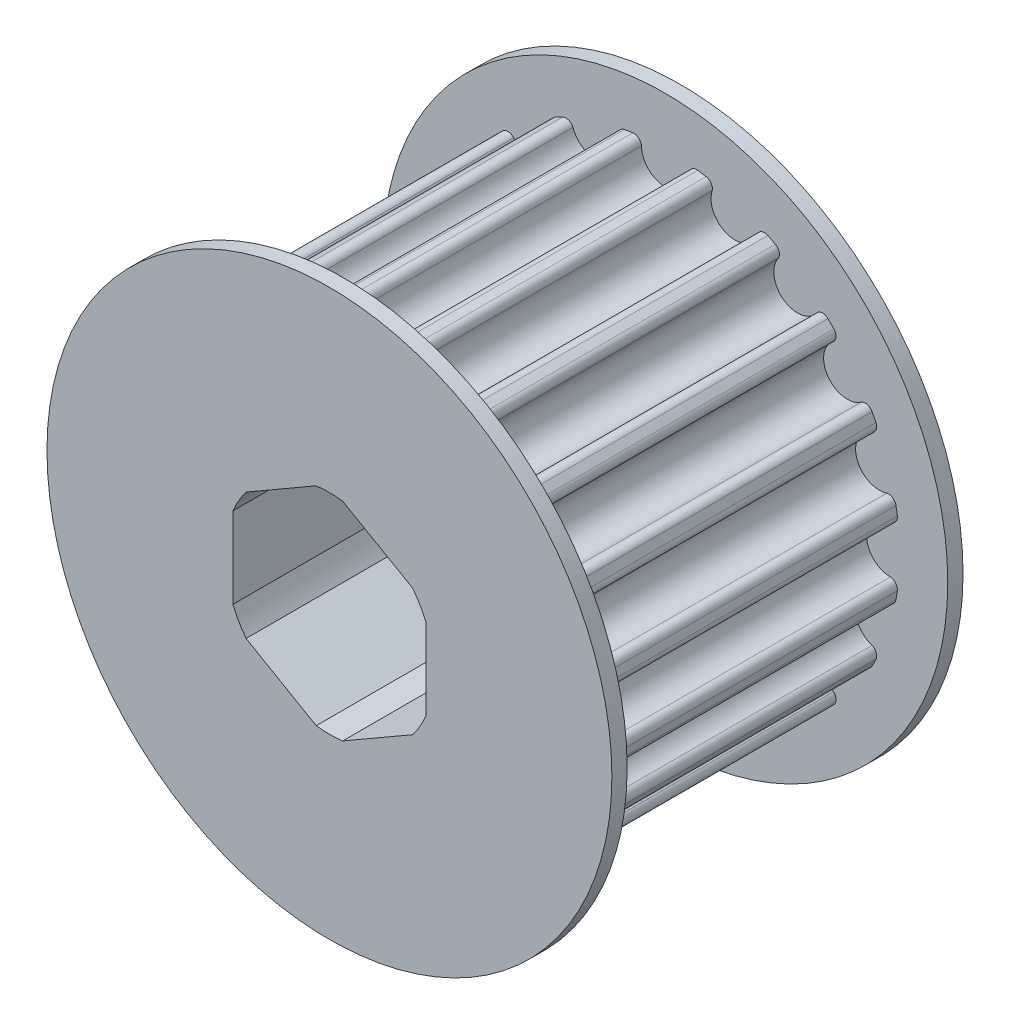
SolidWorks part; units mm, degrees
material "6061-T6 (SS)"
ref_plane "Front Plane" through (0, 0, 0) normal (0, 0, 1) x (1, 0, 0)
ref_plane "Top Plane" through (0, 0, 0) normal (0, 1, 0) x (1, 0, 0)
ref_plane "Right Plane" through (0, 0, 0) normal (1, 0, 0) x (0, 0, -1)
sketch "Pitch diameter" plane through (0, 0, 0) normal (0, 0, 1) x (1, 0, 0)
  circle A0 centre (0, 0) radius 15.9155 construction
  dimension "D1" = 31.831
sketch "Sketch2" plane through (0, 0, 0) normal (0, 0, 1) x (1, 0, 0)
  circle A0 centre (0, 0) radius 15.344
  dimension "D1" = 30.688
extrude "Boss-Extrude1" add sketch "Sketch2" along normal blind 21
sketch "Sketch3" plane through (0, 0, 0) normal (0, 0, -1) x (-1, 0, 0)
  line L0 (-1.6145, 15.2588) -> (-1.56, 14.744)
  line L1 (1.6145, 15.2588) -> (1.56, 14.744)
  line L2 (-1.56, 14.744) -> (1.56, 14.744) construction
  circle A0 centre (0, 0) radius 15.344 construction
  arc A1 (-1.56, 14.744) -> (1.56, 14.744) centre (0, 14.744) ccw
  circle A2 centre (0, 0) radius 15.344 construction
  arc A3 (1.6145, 15.2588) -> (-1.6145, 15.2588) centre (0, 0) ccw
  point P10 (0, 14.744)
  point P15 (0, 13.184)
  point P16 (0, 15.344)
  dimension "D1" = 1.56
  dimension "D2" = 2.16
extrude "Cut-Extrude1" cut sketch "Sketch3" against normal through all
fillet "Fillet1" radius 0.5 2 edges at (-1.6145, 15.2588, 10.5) (1.6145, 15.2588, 10.5)
pattern_circular "CirPattern1" count 20 over 360 about axis through (0, 0, 0) along (0, 0, 1) of "Cut-Extrude1", "Fillet1"
sketch "Sketch5" plane through (0, 0, 0) normal (0, 0, -1) x (-1, 0, 0)
  line L0 (0, 7.303) -> (-0.8658, 6.8031) construction
  line L1 (0.8658, -6.8031) -> (5.4588, -4.1514)
  line L2 (6.3246, -2.6517) -> (6.3246, 2.6517)
  line L3 (5.4588, 4.1514) -> (0.8658, 6.8031)
  line L4 (-0.8658, 6.8031) -> (-5.4588, 4.1514)
  line L5 (-6.3246, 2.6517) -> (-6.3246, -2.6517)
  line L6 (-5.4588, -4.1514) -> (-0.8658, -6.8031)
  line L7 (0.8658, 6.8031) -> (0, 7.303) construction
  line L8 (6.3246, 3.6515) -> (5.4588, 4.1514) construction
  line L9 (6.3246, 2.6517) -> (6.3246, 3.6515) construction
  line L10 (6.3246, -3.6515) -> (6.3246, -2.6517) construction
  line L11 (5.4588, -4.1514) -> (6.3246, -3.6515) construction
  line L12 (-0.8658, -6.8031) -> (0, -7.303) construction
  line L13 (0, -7.303) -> (0.8658, -6.8031) construction
  line L14 (-6.3246, -3.6515) -> (-5.4588, -4.1514) construction
  line L15 (-6.3246, -2.6517) -> (-6.3246, -3.6515) construction
  line L16 (-5.4588, 4.1514) -> (-6.3246, 3.6515) construction
  line L17 (-6.3246, 3.6515) -> (-6.3246, 2.6517) construction
  circle A1 centre (0, 0) radius 6.3246 construction
  arc A2 (-5.4588, 4.1514) -> (-6.3246, 2.6517) centre (0, 0) ccw
  arc A3 (-0.8658, 6.8031) -> (-5.4588, 4.1514) centre (0, 0) ccw construction
  arc A4 (5.4588, 4.1514) -> (0.8658, 6.8031) centre (0, 0) ccw construction
  arc A5 (0.8658, 6.8031) -> (-0.8658, 6.8031) centre (0, 0) ccw
  arc A6 (6.3246, -2.6517) -> (6.3246, 2.6517) centre (0, 0) ccw construction
  arc A7 (6.3246, 2.6517) -> (5.4588, 4.1514) centre (0, 0) ccw
  arc A8 (0.8658, -6.8031) -> (5.4588, -4.1514) centre (0, 0) ccw construction
  arc A9 (5.4588, -4.1514) -> (6.3246, -2.6517) centre (0, 0) ccw
  arc A10 (-5.4588, -4.1514) -> (-0.8658, -6.8031) centre (0, 0) ccw construction
  arc A11 (-0.8658, -6.8031) -> (0.8658, -6.8031) centre (0, 0) ccw
  arc A12 (-6.3246, 2.6517) -> (-6.3246, -2.6517) centre (0, 0) ccw construction
  arc A13 (-6.3246, -2.6517) -> (-5.4588, -4.1514) centre (0, 0) ccw
  dimension "D1" = 12.6492
  dimension "D2" = 12.6492
  dimension "D3" = 13.716
extrude "Cut-Extrude2" cut sketch "Sketch5" against normal through all contours L5 A13 L6 A11 L1 A9 L2 A7 L3 A5 L4 A2 region at (0, 0, 0)
ref_plane "Plane1" through (0, 0, 10.5) normal (0, 0, 1) x (1, 0, 0)
sketch "Sketch7" plane through (0, 0, 21) normal (0, 0, 1) x (1, 0, 0)
  line L18 (6.3246, -2.6517) -> (6.3246, 2.6517)
  line L19 (0.8658, -6.8031) -> (5.4588, -4.1514)
  line L20 (-5.4588, -4.1514) -> (-0.8658, -6.8031)
  line L21 (-6.3246, 2.6517) -> (-6.3246, -2.6517)
  line L22 (-0.8658, 6.8031) -> (-5.4588, 4.1514)
  line L23 (5.4588, 4.1514) -> (0.8658, 6.8031)
  line L24 (6.3246, -2.6517) -> (6.3246, 2.6517)
  line L25 (0.8658, -6.8031) -> (5.4588, -4.1514)
  line L26 (-5.4588, -4.1514) -> (-0.8658, -6.8031)
  line L27 (-6.3246, 2.6517) -> (-6.3246, -2.6517)
  line L28 (-0.8658, 6.8031) -> (-5.4588, 4.1514)
  line L29 (5.4588, 4.1514) -> (0.8658, 6.8031)
  circle A0 centre (0, 0) radius 18.5
  arc A7 (5.4588, -4.1514) -> (6.3246, -2.6517) centre (0, 0) ccw
  arc A8 (-0.8658, -6.8031) -> (0.8658, -6.8031) centre (0, 0) ccw
  arc A9 (-6.3246, -2.6517) -> (-5.4588, -4.1514) centre (0, 0) ccw
  arc A10 (-5.4588, 4.1514) -> (-6.3246, 2.6517) centre (0, 0) ccw
  arc A11 (0.8658, 6.8031) -> (-0.8658, 6.8031) centre (0, 0) ccw
  arc A12 (6.3246, 2.6517) -> (5.4588, 4.1514) centre (0, 0) ccw
  arc A13 (5.4588, -4.1514) -> (6.3246, -2.6517) centre (0, 0) ccw
  arc A14 (-0.8658, -6.8031) -> (0.8658, -6.8031) centre (0, 0) ccw
  arc A15 (-6.3246, -2.6517) -> (-5.4588, -4.1514) centre (0, 0) ccw
  arc A16 (-5.4588, 4.1514) -> (-6.3246, 2.6517) centre (0, 0) ccw
  arc A17 (0.8658, 6.8031) -> (-0.8658, 6.8031) centre (0, 0) ccw
  arc A18 (6.3246, 2.6517) -> (5.4588, 4.1514) centre (0, 0) ccw
  point P5 (-3.7522, -0.6303)
  dimension "D1" = 37
  dimension "D2" = 0
extrude "Boss-Extrude2" add sketch "Sketch7" along normal blind 1
mirror "Mirror1" about plane through (0, 0, 10.5) normal (0, 0, 1) of "Boss-Extrude2"
equation "\"NumberOfTeeth\"= 20"
equation "\"Pitch\"= 5mm"
equation "\"PitchDiameter\"= ( \"Pitch\" * \"NumberOfTeeth\" ) / Pi"
equation "\"OD\"= \"PitchDiameter\" - 0.0225in * 2"
equation "\"D1@Pitch diameter\" = \"PitchDiameter\""
equation "\"D1@Sketch2\"=\"OD\""
equation "\"D1@CirPattern1\"=\"NumberOfTeeth\""
